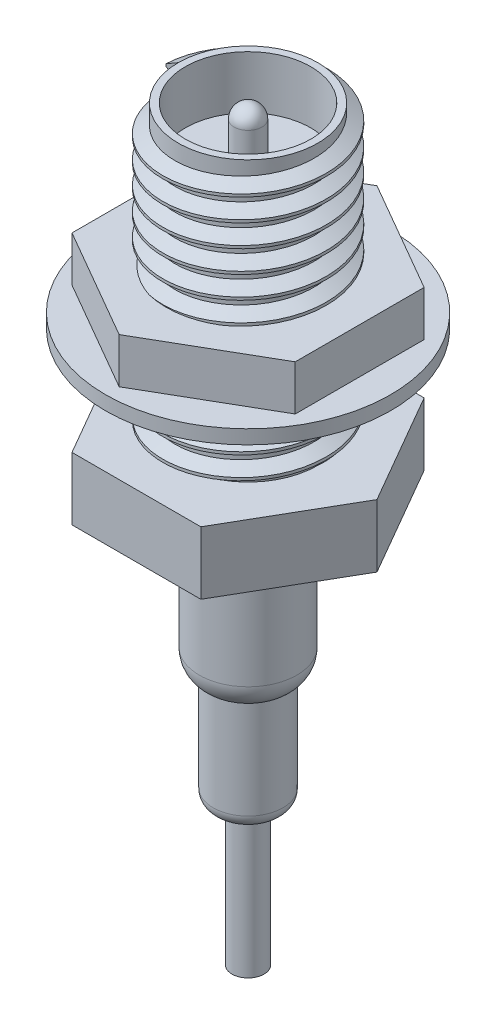
SolidWorks part; units mm, degrees
ref_plane "Front Plane" through (0, 0, 0) normal (0, 0, 1) x (1, 0, 0)
ref_plane "Top Plane" through (0, 0, 0) normal (0, 1, 0) x (1, 0, 0)
ref_plane "Right Plane" through (0, 0, 0) normal (1, 0, 0) x (0, 0, -1)
sketch "Sketch1" plane through (0, 0, 0) normal (0, 1, 0) x (1, 0, 0)
  line L1 (4.6188, 0) -> (2.3094, 4)
  line L2 (2.3094, 4) -> (-2.3094, 4)
  line L3 (-2.3094, 4) -> (-4.6188, 0)
  line L4 (-4.6188, 0) -> (-2.3094, -4)
  line L5 (-2.3094, -4) -> (2.3094, -4)
  line L6 (2.3094, -4) -> (4.6188, 0)
  circle A0 centre (0, 0) radius 4 construction
  dimension "D1" = 8
  dimension "D2" = 4
extrude "Main_hex" add sketch "Sketch1" against normal blind 2.25
sketch "Sketch2" plane through (0, 0, 0) normal (0, 1, 0) x (1, 0, 0)
  circle A0 centre (0, 0) radius 2.5
  dimension "D1" = 5
extrude "Thread_base" add sketch "Sketch2" along normal blind 10 and the other way blind 2.75
thread "Thread" pitch 0.8 method extrude profile "Thread Profile2" start angle 0, offset 0, length 10, pitch 0.8, diameter 5
ref_plane "Plane2" through (-2.5, 10, 0) normal (0, 0, 1) x (-1, 0, 0)
sketch "Thread Profile2" plane through (-2.5, 10, 0) normal (0, 0, 1) x (-1, 0, 0)
  line L0 (0, 0) -> (0, 0.8) construction
  line L1 (0, 0) -> (0.433, 0.25)
  line L2 (0.433, 0.25) -> (0.433, 0.35)
  line L3 (0.433, 0.35) -> (0, 0.6)
  line L4 (0.433, 0.3) -> (0, 0.3) construction
  line L11 (0, 0) -> (0, 0.6)
  point P2 (0, 0)
  dimension "Pitch" = 0.8
  dimension "Profile_Angle" = 60
  dimension "Profile_Land" = 0.1
  dimension "Profile_Height" = 0.433
sketch "Sketch9" plane through (0, 10, 0) normal (0, 1, 0) x (1, 0, 0)
  circle A0 centre (0, 0) radius 2.25
  circle A1 centre (0, 0) radius 0.5
  dimension "D1" = 4.5
  dimension "D2" = 1
extrude "Connector" cut sketch "Sketch9" against normal blind 1.9
fillet "Fillet1" radius 0.5 1 edges at (0, 10, 0.5)
sketch "Sketch10" plane through (0, -2.75, 0) normal (0, -1, 0) x (1, 0, 0)
  circle A0 centre (0, 0) radius 1.75
  dimension "D1" = 3.5
extrude "Boss-Extrude4" add sketch "Sketch10" along normal blind 5
sketch "Sketch11" plane through (0, -7.75, 0) normal (0, -1, 0) x (1, 0, 0)
  circle A0 centre (0, 0) radius 1.25
  dimension "D1" = 2.5
extrude "Boss-Extrude5" add sketch "Sketch11" along normal blind 4
fillet "Fillet2" radius 1 1 edges at (0, -7.75, -1.75)
sketch "Sketch12" plane through (0, -11.75, 0) normal (0, -1, 0) x (1, 0, 0)
  circle A0 centre (0, 0) radius 0.575
  dimension "D1" = 1.15
extrude "Boss-Extrude6" add sketch "Sketch12" along normal blind 5
fillet "Fillet3" radius 0.5 1 edges at (0, -11.75, -1.25)
sketch "Sketch13" plane through (0, 0, 0) normal (0, 1, 0) x (1, 0, 0)
  circle A0 centre (0, 0) radius 5.11
  circle A2 centre (0, 0) radius 3
  dimension "D1" = 10.22
  dimension "D2" = 6
extrude "Washer" add sketch "Sketch13" along normal blind 0.5 from offset 3 separate body
sketch "Sketch14" plane through (0, 3.5, 0) normal (0, 1, 0) x (1, 0, 0)
  line L1 (0, 4.6188) -> (-4, 2.3094)
  line L2 (-4, 2.3094) -> (-4, -2.3094)
  line L3 (-4, -2.3094) -> (0, -4.6188)
  line L4 (0, -4.6188) -> (4, -2.3094)
  line L5 (4, -2.3094) -> (4, 2.3094)
  line L6 (4, 2.3094) -> (0, 4.6188)
  circle A0 centre (0, 0) radius 4 construction
  dimension "D1" = 8
  dimension "D2" = 4
extrude "Hex_nut" add sketch "Sketch14" along normal blind 1.62
